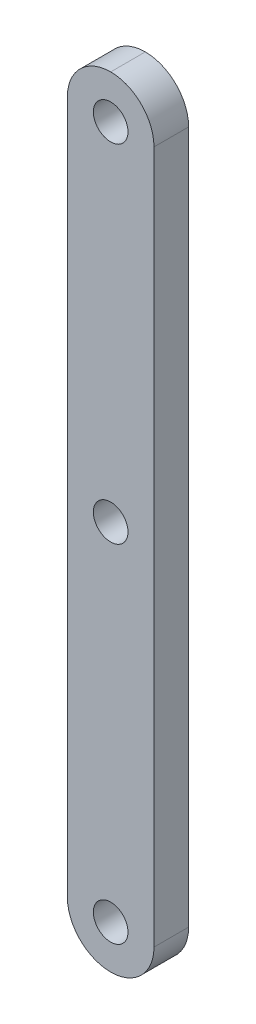
SolidWorks part; units mm, degrees
ref_plane "Plan de face" through (0, 0, 0) normal (0, 0, 1) x (1, 0, 0)
ref_plane "Plan de dessus" through (0, 0, 0) normal (0, 1, 0) x (1, 0, 0)
ref_plane "Plan de droite" through (0, 0, 0) normal (1, 0, 0) x (0, 0, -1)
sketch "Esquisse1" plane through (0, 0, 0) normal (0, 0, 1) x (1, 0, 0)
  line L0 (-25, 225) -> (25, -225) construction
  line L1 (-25, -225) -> (25, -225)
  line L2 (-25, -225) -> (-25, 225)
  line L3 (-25, 225) -> (25, 225)
  line L4 (25, -225) -> (25, 225)
  point P4 (0, 0)
  dimension "D1" = 50
  dimension "D2" = 225
extrude "Boss.-Extru.1" add sketch "Esquisse1" along normal blind 20
sketch "Esquisse2" plane through (0, 0, 20) normal (0, 0, 1) x (1, 0, 0)
  line L0 (-25, -225) -> (25, -225) construction
  line L1 (25, 225) -> (-25, 225) construction
  circle A0 centre (0, -200) radius 10
  circle A1 centre (0, 200) radius 10
  circle A2 centre (0, 0) radius 10
  dimension "D1" = 20
  dimension "D3" = 20
  dimension "D5" = 20
  dimension "D2" = 25
  dimension "D4" = 25
extrude "Enlèv. mat.-Extru.1" cut sketch "Esquisse2" against normal up to next
fillet "Congé1" radius 25 4 edges at (-25, -225, 10) (25, -225, 10) (-25, 225, 10) (25, 225, 10)
